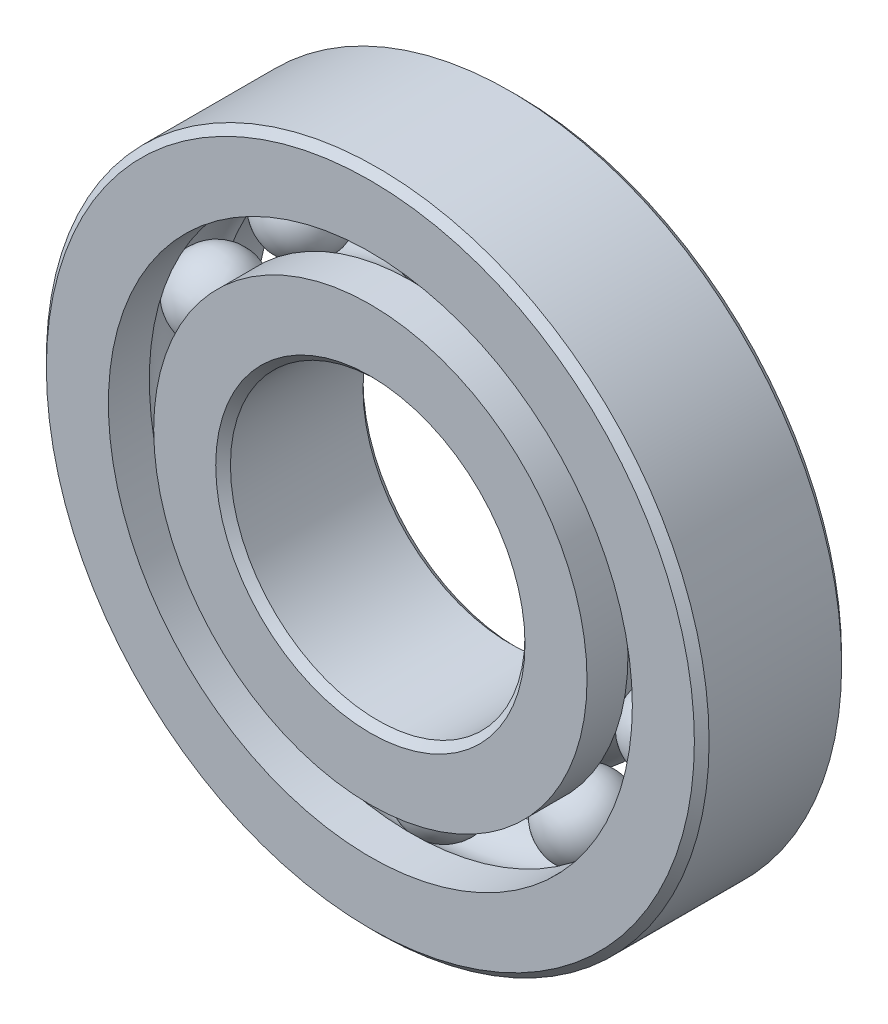
SolidWorks part; units mm, degrees
ref_plane "Front Plane" through (0, 0, 0) normal (0, 0, 1) x (1, 0, 0)
ref_plane "Top Plane" through (0, 0, 0) normal (0, 1, 0) x (1, 0, 0)
ref_plane "Right Plane" through (0, 0, 0) normal (1, 0, 0) x (0, 0, -1)
sketch "Sketch1" plane through (0, 0, 0) normal (1, 0, 0) x (0, 0, -1)
  line L0 (-3.175, 0) -> (3.175, 0) construction
  line L1 (0, 14.2875) -> (0, -14.2875) construction
  line L2 (2.8575, 14.2875) -> (-2.8575, 14.2875)
  line L3 (-2.8575, 14.2875) -> (-3.175, 13.97)
  line L4 (-3.175, 13.97) -> (-3.175, 11.2957)
  line L5 (-3.175, 11.2957) -> (-1.4111, 11.2957)
  line L6 (3.175, 11.2957) -> (1.4111, 11.2957)
  line L7 (3.175, 13.97) -> (3.175, 11.2957)
  line L8 (2.8575, 14.2875) -> (3.175, 13.97)
  line L9 (0, 14.2875) -> (0, 10.3187) construction
  line L10 (0, 10.3187) -> (0, 6.35) construction
  arc A0 (-1.4111, 11.2957) -> (1.4111, 11.2957) centre (0, 10.3187) cw
  point P14 (0, 6.35)
  dimension "D3" = 2.8222
  dimension "D1" = 45
  dimension "Width" = 6.35
  dimension "OD" = 28.575
  dimension "D2" = 0.3175
  dimension "Shaft Dia" = 12.7
  dimension "D4" = 0.9769
revolve "Revolve1" add sketch "Sketch1" angle 360 about L0
sketch "Sketch3" plane through (0, 0, 0) normal (1, 0, 0) x (0, 0, -1)
  line L0 (-3.175, 9.3418) -> (-1.4111, 9.3418)
  line L1 (0, 14.2875) -> (0, -14.2875) construction
  line L2 (-3.175, 13.97) -> (-3.175, 11.2957) construction
  line L3 (-3.175, 9.3418) -> (-3.175, 6.6675)
  line L4 (-2.8575, 14.2875) -> (-3.175, 13.97) construction
  line L5 (-3.175, 6.6675) -> (-2.8575, 6.35)
  line L6 (-2.8575, 6.35) -> (2.8575, 6.35)
  line L7 (2.8575, 14.2875) -> (2.8575, -14.2875) construction
  line L8 (2.8575, 6.35) -> (3.175, 6.6675)
  line L9 (3.175, -13.97) -> (3.175, 13.97) construction
  line L10 (3.175, 6.6675) -> (3.175, 9.3418)
  line L11 (3.175, 9.3418) -> (1.4111, 9.3418)
  line L13 (2.8575, 14.2875) -> (3.175, 13.97) construction
  arc A0 (1.4111, 11.2957) -> (-1.4111, 11.2957) centre (0, 10.3187) ccw construction
  arc A1 (1.4111, 9.3418) -> (-1.4111, 9.3418) centre (0, 10.3187) cw
revolve "Revolve3" add sketch "Sketch3" angle 360 about L0
sketch "Sketch4" plane through (0, 0, 0) normal (1, 0, 0) x (0, 0, -1)
  line L0 (-1.7163, 10.3187) -> (1.7163, 10.3187)
  arc A2 (-1.7163, 10.3187) -> (1.7163, 10.3187) centre (0, 10.3187) cw
  arc A3 (1.4111, 11.2957) -> (-1.4111, 11.2957) centre (0, 10.3187) ccw construction
revolve "Revolve4" add sketch "Sketch4" angle 360 about L0
ref_axis "Axis1" through (0, 0, -3.175) along (0, 0, 1)
pattern_circular "CirPattern1" count 10 every 36 about axis through (0, 0, -3.175) along (0, 0, 1) of bodies 104
sketch "Sketch5" plane through (0, 0, 0) normal (1, 0, 0) x (0, 0, -1)
  line L0 (-3.175, 11.2957) -> (-1.4111, 11.2957) construction
  line L1 (-3.0163, 11.2957) -> (-1.7163, 11.2957)
  line L2 (-3.0163, 11.2957) -> (-3.0163, 9.3418)
  line L3 (-3.0163, 9.3418) -> (-1.7163, 9.3418)
  line L4 (-1.7163, 11.2957) -> (-1.7163, 9.3418)
  line L5 (-3.175, 9.3418) -> (-1.4111, 9.3418) construction
  line L6 (3.175, 11.2957) -> (1.4111, 11.2957) construction
  line L7 (3.0163, 11.2957) -> (1.7163, 11.2957)
  line L8 (3.0163, 11.2957) -> (3.0163, 9.3418)
  line L9 (3.0163, 9.3418) -> (1.7163, 9.3418)
  line L10 (1.7163, 11.2957) -> (1.7163, 9.3418)
  line L11 (3.175, 9.3418) -> (1.4111, 9.3418) construction
  line L12 (-2.8575, 14.2875) -> (-3.175, 13.97) construction
  point P18 (-3.0163, 14.1287)
revolve "Revolve5" [suppressed] add sketch "Sketch5" angle 360 about L0
equation "\"D2@Sketch1\" = \"Width@Sketch1\"*.05"
equation "\"D3@Sketch1\" = \"Width@Sketch1\"/2.25"
equation "\"D4@Sketch1\" = (((\"OD@Sketch1\"-\"Width@Sketch1\")/2)/3.25)/3.5"
equation "\"D2@CirPattern1\" = 360/\"Balls@CirPattern1\""
